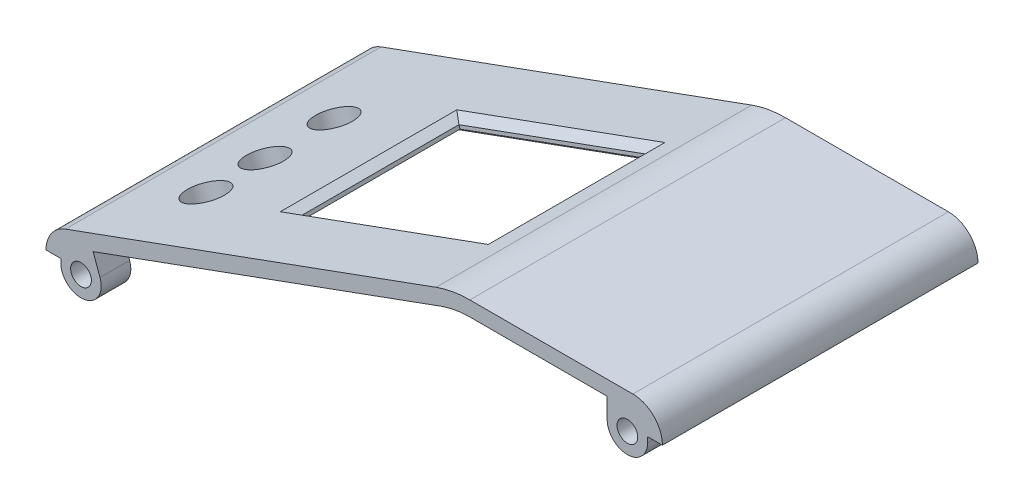
SolidWorks part; units mm, degrees
ref_plane "Спереди" through (0, 0, 0) normal (0, 0, 1) x (1, 0, 0)
ref_plane "Сверху" through (0, 0, 0) normal (0, 1, 0) x (1, 0, 0)
ref_plane "Справа" through (0, 0, 0) normal (1, 0, 0) x (0, 0, -1)
sketch "Эскиз1" plane through (0, 0, 0) normal (0, 0, 1) x (1, 0, 0)
  line L1 (56.5, 80) -> (23.4509, 80)
  line L5 (-57.5261, 48.6178) -> (17.6365, 75.9748)
  line L6 (23.4509, 77) -> (56.5, 77)
  line L10 (-56.5, 0) -> (56.5, 0) construction
  line L12 (-58.5521, 51.4369) -> (16.6105, 78.7939)
  line L13 (-62.5, 7.8203) -> (-62.5, 50) construction
  line L14 (-62.5, 45.7988) -> (-62.5, 6) construction
  line L15 (19.9243, 80) -> (-62.5, 50) construction
  line L16 (-59.5, 45.7988) -> (-62.5, 45.7988)
  line L17 (62.5, 39.659) -> (62.5, 80) construction
  line L18 (62.5, 6) -> (62.5, 74) construction
  line L19 (19.9243, 80) -> (62.5, 80) construction
  line L20 (62.5, 74) -> (59.5, 74)
  arc A0 (23.4509, 80) -> (16.6105, 78.7939) centre (23.4509, 60) ccw
  arc A1 (17.6365, 75.9748) -> (23.4509, 77) centre (23.4509, 60) cw
  arc A2 (-58.5521, 51.4369) -> (-62.5, 45.7988) centre (-56.5, 45.7988) ccw
  arc A4 (-57.5261, 48.6178) -> (-59.5, 45.7988) centre (-56.5, 45.7988) ccw
  arc A7 (56.5, 80) -> (62.5, 74) centre (56.5, 74) cw
  arc A8 (56.5, 77) -> (59.5, 74) centre (56.5, 74) cw
  dimension "D3" = 20
  dimension "D4" = 17
  dimension "D8" = 6
  dimension "D9" = 6
  dimension "D1" = 3
  dimension "D2" = 20
  dimension "D5" = 80
  dimension "D6" = 3
  dimension "D7" = 50
extrude "Бобышка-Вытянуть1" add sketch "Эскиз1" along normal mid plane 64
sketch "Эскиз2" plane through (0, 0, 0) normal (0, 0, 1) x (1, 0, 0)
  line L1 (45.7459, 80) -> (68.9106, 80) construction
  line L6 (56.5, 80) -> (23.4509, 80) construction
  line L15 (59.5, 74) -> (59.5, 72.9)
  line L16 (59.5, 74) -> (59.5, 10.2) construction
  line L17 (51.3, 72.9) -> (51.3, 77)
  line L18 (23.4509, 77) -> (56.5, 77) construction
  line L20 (65.2864, 82.7864) -> (47.2543, 64.7543) construction
  line L21 (56.5, 77) -> (51.3, 77)
  line L22 (-71.1179, 56.0343) -> (-34.3237, 30.2708) construction
  line L23 (-62.5, 45.7988) -> (-62.5, 6) construction
  line L24 (-59.5, 10.2) -> (-59.5, 45.7988) construction
  line L25 (-59.5, 45.7988) -> (-59.5, 45.0285)
  line L26 (-51.5473, 46.4308) -> (-52.9495, 50.2835)
  line L27 (-57.5261, 48.6178) -> (17.6365, 75.9748) construction
  line L28 (-52.9495, 50.2835) -> (-57.5261, 48.6178)
  circle A1 centre (55.4, 72.9) radius 2.1
  circle A3 centre (-55.4, 45.0285) radius 2.1
  arc A4 (-58.5521, 51.4369) -> (-62.5, 45.7988) centre (-56.5, 45.7988) ccw construction
  arc A8 (59.5, 74) -> (56.5, 77) centre (56.5, 74) ccw construction
  arc A9 (59.5, 74) -> (56.5, 77) centre (56.5, 74) ccw
  arc A10 (59.5, 72.9) -> (51.3, 72.9) centre (55.4, 72.9) cw
  arc A11 (-59.5, 45.0285) -> (-51.5473, 46.4308) centre (-55.4, 45.0285) ccw
  arc A12 (-57.5261, 48.6178) -> (-59.5, 45.7988) centre (-56.5, 45.7988) ccw construction
  arc A13 (-57.5261, 48.6178) -> (-59.5, 45.7988) centre (-56.5, 45.7988) ccw
  point P12 (-61.4149, 49.2402)
  point P26 (58.6213, 76.1213)
  dimension "D1" = 4.2
  dimension "D2" = 45
  dimension "D3" = 2
  dimension "D4" = 55
  dimension "D5" = 2
  dimension "D6" = 2
extrude "Бобышка-Вытянуть2" add sketch "Эскиз2" against normal blind 6 from surface contours A1 | A1 | A3 | A3 region at (59.384, 73.45, 0) region at (-58.8556, 47.4481, 0) region at (55.4, 72.9, 0) region at (-55.4, 45.0285, 0) starting at face at (6.542, 67.6477, 32)
extrude "Бобышка-Вытянуть3" add sketch "Эскиз2<3>" along normal blind 6 from surface contours A1 | A1 | A3 | A3 region at (59.384, 73.45, 0) region at (-58.8556, 47.4481, 0) region at (55.4, 72.9, 0) region at (-55.4, 45.0285, 0) starting at face at (6.542, 67.6477, -32)
sketch "Эскиз2<3>" plane through (0, 0, 0) normal (0, 0, 1) x (1, 0, 0) same geometry as "Эскиз2"
extrude "Вырез-Вытянуть1" cut sketch "Эскиз2<4>" against normal blind 4 from surface contours A1 | A3 region at (55.4, 72.9, 0) region at (-55.4, 45.0285, 0) starting at face at (4.8932, 65.0579, 32)
sketch "Эскиз2<4>" plane through (0, 0, 0) normal (0, 0, 1) x (1, 0, 0) same geometry as "Эскиз2"
extrude "Вырез-Вытянуть2" cut sketch "Эскиз2<5>" along normal blind 4 from surface contours A1 | A3 region at (55.4, 72.9, 0) region at (-55.4, 45.0285, 0) starting at face at (4.8932, 65.0579, -32)
sketch "Эскиз2<5>" plane through (0, 0, 0) normal (0, 0, 1) x (1, 0, 0) same geometry as "Эскиз2"
sketch "Эскиз3" plane through (-22.3547, 61.4191, 0) normal (0.342, -0.9397, 0) x (0.9397, 0.342, 0)
  line L8 (-9.7778, -17.5) -> (-9.7778, -14.8)
  line L9 (38.4222, -17.5) -> (-9.7778, -17.5)
  line L10 (38.4222, 17.5) -> (38.4222, -17.5)
  line L11 (-9.5778, 17.5) -> (38.4222, 17.5)
  line L12 (-9.7778, -17.5) -> (-9.7778, 17.5)
  line L13 (38.4222, -17.5) -> (-9.7778, -17.5)
  line L14 (38.4222, 17.5) -> (38.4222, -17.5)
  line L15 (-9.7778, 17.5) -> (38.4222, 17.5)
  dimension "D1" = 0.2
extrude "Вырез-Вытянуть3" cut sketch "Эскиз3" against normal blind 0.8
sketch "Эскиз4" plane through (-22.3547, 61.4191, 0) normal (0.342, -0.9397, 0) x (0.9397, 0.342, 0)
  line L16 (-4.5778, -16.4) -> (37.3222, -16.4)
  line L17 (-4.5778, 16.4) -> (-4.5778, -16.4)
  line L18 (37.3222, 16.4) -> (-4.5778, 16.4)
  line L19 (37.3222, -16.4) -> (37.3222, 16.4)
  line L20 (-4.5778, -16.4) -> (37.3222, -16.4)
  line L21 (-4.5778, 16.4) -> (-4.5778, -16.4)
  line L22 (37.3222, 16.4) -> (-4.5778, 16.4)
  line L23 (37.3222, -16.4) -> (37.3222, 16.4)
  dimension "D1" = 0.5
extrude "Вырез-Вытянуть4" cut sketch "Эскиз4" against normal through all
sketch "Эскиз7" plane through (-23.3808, 64.2382, 0) normal (-0.342, 0.9397, 0) x (0.9397, 0.342, 0)
  circle A2 centre (-24.4278, 10.25) radius 4
  circle A3 centre (-24.4278, 10.25) radius 4
  circle A20 centre (-24.4128, -3.75) radius 4
  circle A21 centre (-24.4128, -15.75) radius 4
  dimension "D2" = 8
  dimension "D1" = 0.5
extrude "Вырез-Вытянуть5" cut sketch "Эскиз7" against normal blind 10
sketch "Эскиз8" plane through (-22.3547, 61.4191, 0) normal (0.342, -0.9397, 0) x (0.9397, 0.342, 0)
  line L0 (38.4222, -17.5) -> (38.4222, 17.5) construction
  circle A1 centre (40.9722, 15) radius 2.55
  circle A4 centre (40.9722, -15) radius 2.55
  circle A7 centre (-36.0278, -16.5) radius 2.55
  circle A8 centre (-36.0278, 16.5) radius 2.55
extrude "Бобышка-Вытянуть4" add sketch "Эскиз8" along normal up to surface (2 mm away)
sketch "Эскиз9" plane through (-21.6707, 59.5398, 0) normal (0.342, -0.9397, 0) x (0.9397, 0.342, 0)
  circle A0 centre (40.9722, -15) radius 1.4
  circle A1 centre (40.9722, 15) radius 1.4
  circle A2 centre (-36.0278, -16.5) radius 1.4
  circle A3 centre (-36.0278, 16.5) radius 1.4
  dimension "D1" = 2.8
extrude "Вырез-Вытянуть6" cut sketch "Эскиз9" against normal blind 3
chamfer "Фаска1" distance 1.5 angle 45 4 edges at (-27.6826, 62.6725, 0) (-7.996, 69.8378, -16.4) (11.6906, 77.0032, 0) (-7.996, 69.8378, 16.4)
